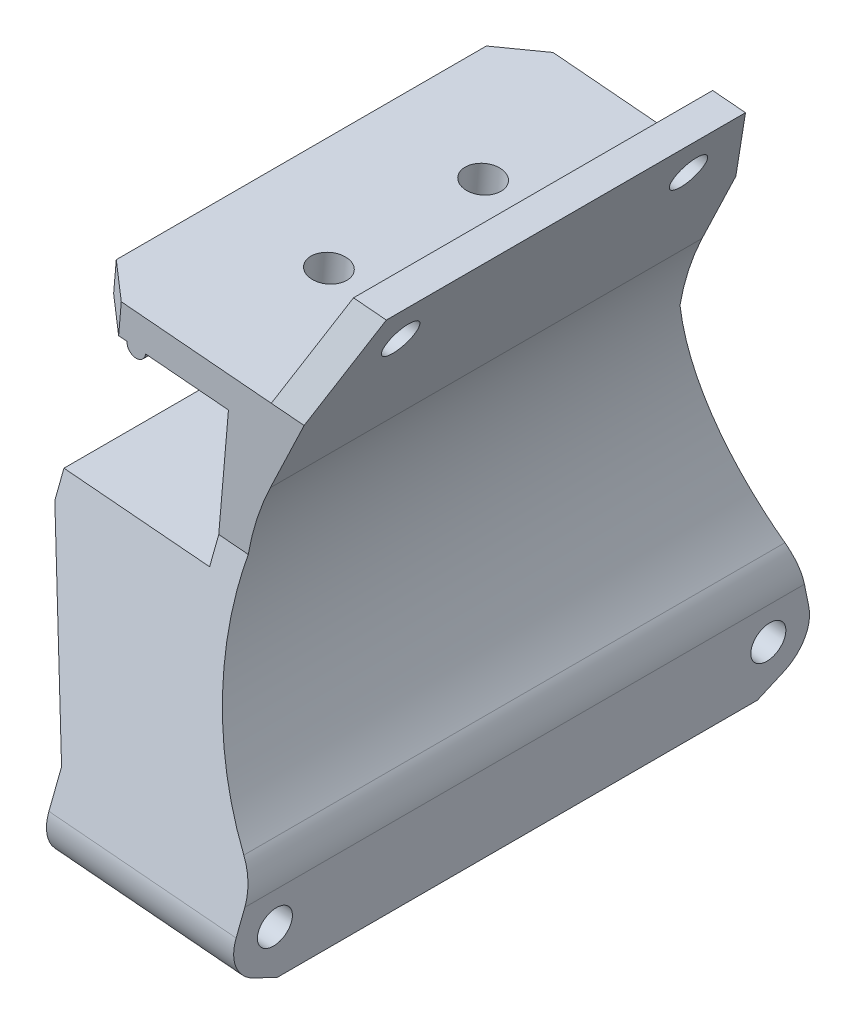
SolidWorks part; units mm, degrees
ref_plane "Front Plane" through (0, 0, 0) normal (0, 0, 1) x (1, 0, 0)
ref_plane "Top Plane" through (0, 0, 0) normal (0, 1, 0) x (1, 0, 0)
ref_plane "Right Plane" through (0, 0, 0) normal (1, 0, 0) x (0, 0, -1)
sketch "Sketch2" plane through (13.4518, -30.2663, 128.4516) normal (0, 0, -1) x (-0.9963, 0.0858, 0)
  line L0 (34, 0) -> (34, 8.2154) construction
  line L1 (40.336, 38.152) -> (34, 55) construction
  line L2 (34, 0) -> (34, 8.2154)
  line L3 (40.336, 38.152) -> (34, 55)
  line L4 (34, 0) -> (52.2773, 0)
  line L5 (52.2773, 9.3) -> (59, 26.3)
  line L6 (52.2773, 0) -> (52.2773, 9.3)
  line L7 (59, 31.3) -> (44.7773, 31.3)
  line L8 (44.7773, 42.3) -> (52.8773, 42.3)
  line L9 (59, 42.3) -> (59, 45.3)
  line L10 (59, 45.3) -> (40.853, 45.3)
  line L11 (40.853, 45.3) -> (37.2051, 55)
  line L12 (37.2051, 55) -> (34, 55)
  line L13 (44.7773, 42.3) -> (44.7773, 31.3) construction
  line L14 (44.7773, 42.3) -> (44.7773, 31.3)
  line L15 (52.2773, 8.7816) -> (52.2773, 1.2268) construction
  line L16 (59, 26.3) -> (59, 31.3)
  line L17 (62.7784, 31.3) -> (57.4884, 31.3) construction
  line L18 (54.6773, 42.3) -> (59, 42.3)
  arc A0 (35.2903, 11.5677) -> (34, 8.2154) centre (39, 8.2154) ccw construction
  arc A1 (35.2903, 11.5677) -> (40.336, 38.152) centre (16, 29) ccw construction
  arc A2 (35.2903, 11.5677) -> (34, 8.2154) centre (39, 8.2154) ccw
  arc A3 (35.2903, 11.5677) -> (40.336, 38.152) centre (16, 29) ccw
  arc A4 (52.8773, 42.3) -> (54.6773, 42.3) centre (53.7773, 42.3) ccw construction
  arc A5 (52.8773, 42.3) -> (54.6773, 42.3) centre (53.7773, 42.3) ccw
  dimension "D1" = 3
  dimension "D2" = 25
  dimension "D3" = 3
  dimension "D4" = 5
extrude "Boss-Extrude1" add sketch "Sketch2" along normal mid plane 60
sketch "Sketch3" plane through (1.3991, 16.2398, 0) normal (0.0858, 0.9963, 0) x (0.9963, -0.0858, 0)
  line L1 (-43, -98.4516) -> (-29, -98.4516)
  line L3 (-43, -110.4516) -> (-43, -98.4516)
  line L4 (-43, -110.4516) -> (-29, -98.4516)
  line L5 (-43, -128.4516) -> (-19.1738, -128.4516) construction
  line L6 (-43, -98.4516) -> (-43, -158.4516) construction
  line L11 (-43, -146.4516) -> (-29, -158.4516)
  line L12 (-43, -146.4516) -> (-43, -158.4516)
  line L13 (-43, -158.4516) -> (-29, -158.4516)
  dimension "D1" = 12
  dimension "D2" = 14
extrude "Cut-Extrude1" cut sketch "Sketch3" against normal up to surface (3 mm away) up to face at (-31.5645, 16.0686, 128.4516)
sketch "Sketch4" plane through (-42.8413, 3.6909, 0) normal (-0.9963, 0.0858, 0) x (0, 0, 1)
  line L0 (100.5894, -23.159) -> (107.4516, 2.3)
  line L2 (98.4516, 2.3) -> (158.4516, 2.3) construction
  line L3 (158.4516, -29) -> (158.4516, 26)
  line L4 (151.8053, -29) -> (158.4516, -29)
  line L5 (145.9211, 26) -> (158.4516, 26)
  line L6 (149.4516, 16.3) -> (145.9211, 26)
  line L7 (149.4516, 2.3) -> (149.4516, 16.3)
  line L8 (154.246, -27.7749) -> (151.8053, -29)
  line L9 (156.3138, -23.159) -> (149.4516, 2.3)
  line L12 (102.6572, -27.7749) -> (105.0979, -29)
  line L15 (107.4516, 2.3) -> (107.4516, 16.3)
  line L16 (110.4516, 16.3) -> (98.4516, 16.3) construction
  line L17 (107.4516, 16.3) -> (110.9821, 26)
  line L19 (110.9821, 26) -> (98.4516, 26)
  line L20 (128.4516, 16.3) -> (128.4516, -39.4935) construction
  line L24 (105.0979, -29) -> (98.4516, -29)
  line L25 (98.4516, -29) -> (98.4516, 26)
  line L26 (98.4516, 26) -> (158.4516, 26) construction
  line L28 (110.4516, 16.3) -> (146.4516, 16.3) construction
  arc A0 (156.3138, -23.159) -> (154.246, -27.7749) centre (152.4516, -24.2) cw
  arc A4 (100.5894, -23.159) -> (102.6572, -27.7749) centre (104.4516, -24.2) ccw
  dimension "D1" = 4
  dimension "D3" = 9
  dimension "D4" = 110
  dimension "D2" = 6
  dimension "D5" = 4.8
  dimension "D6" = 6.6463
extrude "Cut-Extrude2" cut sketch "Sketch4" against normal blind 60
sketch "Sketch6" plane through (13.4518, -30.2663, 128.4516) normal (0, 0, -1) x (-0.9963, 0.0858, 0)
  line L0 (52.2773, 0) -> (52.2773, 2.5)
  line L1 (52.2773, 1.2251) -> (52.2773, 5.841) construction
  line L2 (52.2773, 0) -> (52.2773, 2.5) construction
  line L3 (52.2773, 2.5) -> (47.7773, 0)
  line L5 (47.7773, 0) -> (52.2773, 0)
  line L6 (34, 0) -> (52.2773, 0) construction
  dimension "D1" = 4.5
  dimension "D2" = 2.5
extrude "Cut-Extrude3" cut sketch "Sketch6" along normal mid plane 30
sketch "Sketch7" plane through (1.3991, 16.2398, 0) normal (0.0858, 0.9963, 0) x (0.9963, -0.0858, 0)
  line L0 (-43, -128.4516) -> (-13.0603, -128.4516) construction
  line L1 (-43, -110.4516) -> (-43, -146.4516) construction
  line L2 (-18, -128.4516) -> (16, -128.4516) construction
  line L4 (-36.2773, -101.5218) -> (-36.2773, -155.3814) construction
  circle A0 centre (-32.7773, -135.9516) radius 1.75
  circle A1 centre (-32.7773, -120.9516) radius 1.75
  dimension "D1" = 3.5
  dimension "D2" = 3.5
  dimension "D3" = 7.5
extrude "Cut-Extrude4" cut sketch "Sketch7" against normal up to surface (3 mm away) up to face at (-31.5645, 16.0686, 128.4516)
hole_wizard "M3x0.5 Tapped Hole1" positions "Sketch8" profile "Sketch9" tap size "M3x0.5" standard "ANSI Metric"
sketch "Sketch8" plane through (0.1974, 2.2915, 0) normal (0.0858, 0.9963, 0) x (0.9963, -0.0858, 0)
  circle A0 centre (-32.7773, -120.9516) radius 1.75 construction
  circle A1 centre (-32.7773, -135.9516) radius 1.75 construction
  point P0 (-32.7773, -135.9516)
  point P2 (-32.7773, -120.9516)
sketch "Sketch9" plane through (-32.4589, 5.1049, 135.9516) normal (0, 0, 1) x (-0.9963, 0.0858, 0)
  line L0 (0, 0) -> (0, 9.2511)
  line L1 (0, 9.2511) -> (1.25, 8.5)
  line L2 (1.25, 8.5) -> (1.25, 0)
  line L5 (1.25, 0) -> (0, 0)
  line L10 (0, 9.2511) -> (-1.25, 8.5) construction
  line L11 (0, -6.35) -> (0, 107.95) construction
  dimension "Tap Drill Dia." = 2.5
  dimension "Tap Drill Depth" = 8.5
  dimension "Drill Angle" = 118
cosmetic thread "Hole Thread1" parameters "D1"=6, "D2"=3
cosmetic thread "Hole Thread2" parameters "D1"=6, "D2"=3
hole_wizard "M3 Clearance Hole1" positions "Sketch11" profile "Sketch12" hole size "M3" standard "ANSI Metric" end condition through all
sketch "Sketch11" plane through (-36.1434, 3.1138, 0) normal (-0.9963, 0.0858, 0) x (0, 0, 1)
  line L0 (128.4516, -26.5) -> (128.4516, -7.7775) construction
  line L1 (113.4516, -26.5) -> (143.4516, -26.5) construction
  line L3 (105.0979, -29) -> (113.4516, -29) construction
  point P0 (104.4516, -24.2)
  point P2 (152.4516, -24.2)
  dimension "D1" = 48
  dimension "D2" = 24
  dimension "D3" = 4.8
sketch "Sketch12" plane through (-38.2205, -20.9969, 104.4516) normal (0, 0, 1) x (-0.0858, -0.9963, 0)
  line L0 (0, 0) -> (0, 22.9807)
  line L1 (0, 22.9807) -> (1.7, 22.9807)
  line L2 (1.7, 22.9807) -> (1.7, 0)
  line L5 (1.7, 0) -> (0, 0)
  line L11 (0, -6.35) -> (0, 107.95) construction
  dimension "Thru Hole Dia." = 3.4
  dimension "Thru Hole Depth" = 22.9807
hole_wizard "M3 Clearance Hole3" positions "Sketch15" profile "Sketch16" hole size "M3" standard "ANSI Metric" end condition through all
sketch "Sketch15" plane through (-42.8413, 3.6909, 0) normal (-0.9963, 0.0858, 0) x (0, 0, 1)
  line L0 (110.9821, 26) -> (145.9211, 26) construction
  line L1 (128.4516, -29) -> (128.4516, 43.6674) construction
  line L2 (113.4516, -29) -> (143.4516, -29) construction
  point P0 (114.4516, 21.5)
  point P2 (142.4516, 21.5)
  dimension "D1" = 4.5
  dimension "D2" = 14
  dimension "D3" = 28
sketch "Sketch16" plane through (-40.9959, 25.1115, 114.4516) normal (0, 0, 1) x (-0.0858, -0.9963, 0)
  line L0 (0, 0) -> (0, 29.7034)
  line L1 (0, 29.7034) -> (1.7, 29.7034)
  line L2 (1.7, 29.7034) -> (1.7, 0)
  line L5 (1.7, 0) -> (0, 0)
  line L11 (0, -6.35) -> (0, 107.95) construction
  dimension "Thru Hole Dia." = 3.4
  dimension "Thru Hole Depth" = 29.7034
sketch "Sketch17" plane through (-42.8413, 3.6909, 0) normal (-0.9963, 0.0858, 0) x (0, 0, 1)
  circle A0 centre (114.4516, 21.5) radius 2.5
  circle A1 centre (142.4516, 21.5) radius 2.5
  dimension "D1" = 5
  dimension "D2" = 5
extrude "Cut-Extrude5" cut sketch "Sketch17" against normal blind 21
sketch "Sketch18" plane through (0, 0, 107.4516) normal (0, 0, -1) x (-1, 0, 0)
  line L1 (28.4736, 4.7616) -> (42.6439, 5.9824)
  line L2 (28.4736, 4.7616) -> (28.6882, 2.2708)
  line L3 (28.6882, 2.2708) -> (42.8585, 3.4916)
  line L4 (42.6439, 5.9824) -> (42.8585, 3.4916)
  line L6 (28.4736, 4.7616) -> (42.6439, 5.9824) construction
  line L7 (43.0731, 1.0008) -> (42.6439, 5.9824) construction
  line L8 (27.5295, 15.721) -> (28.4736, 4.7616) construction
  dimension "D1" = 2.5
extrude "Cut-Extrude6" cut sketch "Sketch18" against normal up to surface and the other way blind 10 up to face at (-30.8785, -8.5595, 153.0845)
